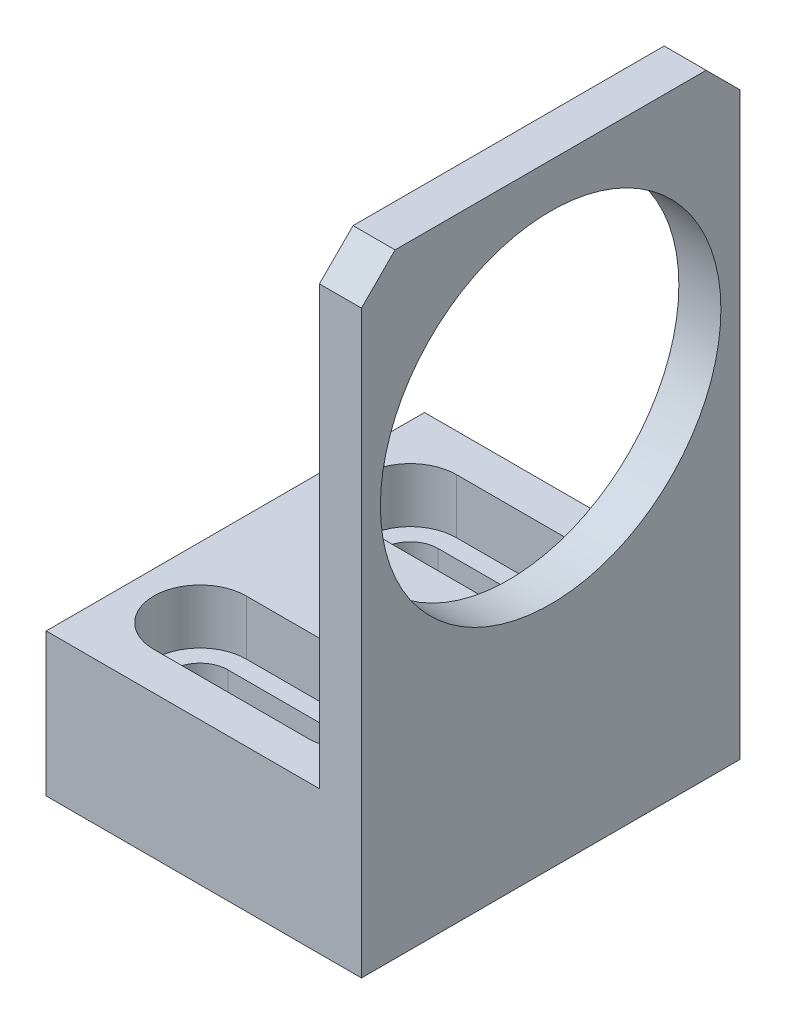
SolidWorks part; units mm, degrees
ref_plane "Front" through (0, 0, 0) normal (0, 0, 1) x (1, 0, 0)
ref_plane "Top" through (0, 0, 0) normal (0, 1, 0) x (1, 0, 0)
ref_plane "Right" through (0, 0, 0) normal (1, 0, 0) x (0, 0, -1)
sketch "Sketch1" plane through (0, 0, 0) normal (1, 0, 0) x (0, 0, -1)
  line L1 (-22.5, 0) -> (22.5, 0)
  line L2 (-22.5, 0) -> (-22.5, 73)
  line L3 (-22.5, 73) -> (22.5, 73)
  line L4 (22.5, 0) -> (22.5, 73)
  circle A0 centre (0, 47.5) radius 20.25
  dimension "D3" = 40.5
  dimension "D1" = 45
  dimension "D2" = 73
  dimension "D4" = 47.5
extrude "Boss-Extrude1" add sketch "Sketch1" along normal blind 5
cosmetic thread "Cosmetic Thread1" parameters "D2"=41
chamfer "Chamfer1" distance 4 angle 45 2 edges at (2.5, 73, -22.5) (2.5, 73, 22.5)
sketch "Sketch2" plane through (0, 0, 0) normal (-1, 0, 0) x (0, 0, 1)
  line L3 (-22.5, 0) -> (-22.5, 17)
  line L4 (-22.5, 0) -> (-22.5, 69) construction
  line L5 (-22.5, 17) -> (22.5, 17)
  line L15 (22.5, 69) -> (22.5, 0) construction
  line L16 (22.5, 17) -> (22.5, 0)
  line L17 (22.5, 0) -> (-22.5, 0)
  dimension "D2" = 17
extrude "Boss-Extrude2" add sketch "Sketch2" along normal blind 32.5 contours L3 L5 L16 L17
hole_wizard "CBORE SLOT for M6 Hex Socket Head Cap Screw1" positions "Sketch3" profile "Sketch4" size "M6" standard "DIN" slot yes end condition up to next
sketch "Sketch3" plane through (0, 17, 0) normal (0, 1, 0) x (1, 0, 0)
  line L0 (-27.5, 12.5) -> (-2.5, 12.5) construction
  line L1 (-32.5, 22.5) -> (-32.5, -22.5) construction
  point P0 (-15, 12.5)
  point P4 (-15, -12.5)
  dimension "D1" = 25
  dimension "D2" = 17.5
  dimension "D3" = 12.5
  dimension "D4" = 12.5
sketch "Sketch4" plane through (-15, 17, -12.5) normal (1, 0, 0) x (0, 0, 1)
  line L0 (0, 0) -> (0, 17)
  line L1 (0, 17) -> (3.3, 17)
  line L3 (3.3, 17) -> (3.3, 6.5)
  line L4 (3.3, 6.5) -> (5.5, 6.5)
  line L5 (5.5, 6.5) -> (5.5, 0)
  line L7 (5.5, 0) -> (0, 0)
  line L11 (0, -6.35) -> (0, 107.95) construction
  dimension "Thru Hole Dia." = 6.6
  dimension "Thru Hole Depth" = 17
  dimension "C'Bore Dia." = 11
  dimension "C'Bore Depth" = 6.5
